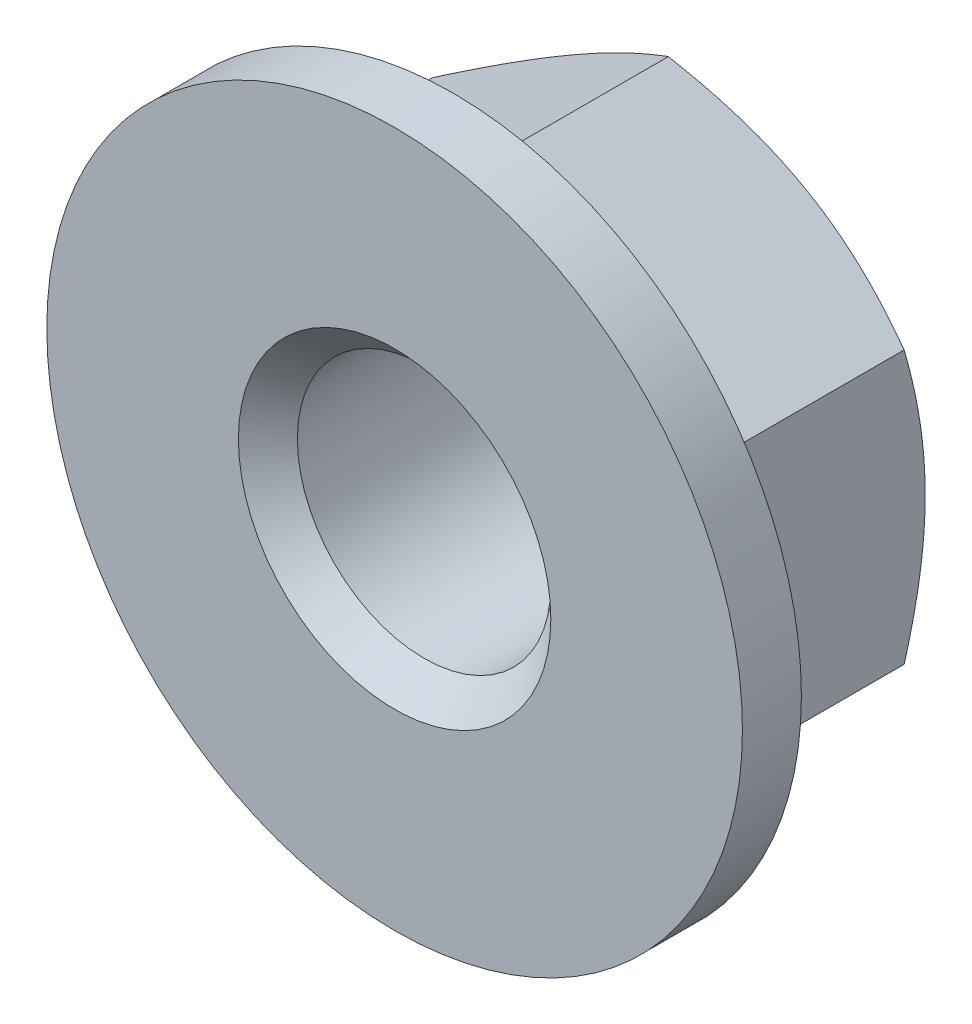
SolidWorks part; units mm, degrees
note: '?' marks a value the reader was unsure of.
ref_plane "前视基准面" through (0, 0, 0) normal (0, 0, 1) x (1, 0, 0)
ref_plane "上视基准面" through (0, 0, 0) normal (0, 1, 0) x (1, 0, 0)
ref_plane "右视基准面" through (0, 0, 0) normal (1, 0, 0) x (0, 0, -1)
sketch "草图1" plane through (0, 0, 0) normal (0, 0, 1) x (1, 0, 0)
  line L1 (0, 4.6188) -> (-4, 2.3094)
  line L2 (-4, 2.3094) -> (-4, -2.3094)
  line L3 (-4, -2.3094) -> (0, -4.6188)
  line L4 (0, -4.6188) -> (4, -2.3094)
  line L5 (4, -2.3094) -> (4, 2.3094)
  line L6 (4, 2.3094) -> (0, 4.6188)
  circle A0 centre (0, 0) radius 4 construction
  dimension "D2" = 8
extrude "凸台-拉伸1" add sketch "草图1" against normal blind 4
sketch "草图2" plane through (0, 0, 0) normal (1, 0, 0) x (0, 0, -1)
  line L0 (0, 4.6188) -> (0.3573, 4.6188)
  line L1 (0, 4.6188) -> (0, 4)
  line L2 (4, 4.6188) -> (0, 4.6188) construction
  line L3 (0.3573, 4.6188) -> (0, 4)
  line L5 (0, 0) -> (4, 0) construction
  line L6 (4, -2.3094) -> (4, 2.3094) construction
  line L7 (4, 4) -> (3.6427, 4.6188)
  line L8 (4, 2.3094) -> (4, 4.6188) construction
  line L9 (3.6427, 4.6188) -> (4, 4.6188)
  line L10 (4, 4.6188) -> (4, 4)
  dimension "D1" = 8
  dimension "D2" = 30
revolve "切除-旋转1" cut sketch "草图2" angle 360 about L5
sketch "草图3" plane through (0, 0, 0) normal (0, 0, 1) x (1, 0, 0)
  circle A0 centre (0, 0) radius 5.9
  dimension "D1" = 11.8
extrude "凸台-拉伸2" add sketch "草图3" along normal blind 1
sketch "草图4" plane through (0, 0, -4) normal (0, 0, -1) x (-1, 0, 0)
  circle A0 centre (0, 0) radius 2.15
  dimension "D1" = 4.3
extrude "切除-拉伸1" cut sketch "草图4" against normal through all
cosmetic thread "装饰螺纹线1"
chamfer "倒角1" distance 0.5 angle 45 2 edges at (-2.15, 0, -4) (-2.15, 0, 1)
sketch "草图5" plane through (0, 0, 0) normal (0, 0, 1) x (1, 0, 0)
  line L1 (0, 4.6188) -> (-4, 2.3094)
  line L2 (-4, 2.3094) -> (-4, -2.3094)
  line L3 (-4, -2.3094) -> (0, -4.6188)
  line L4 (0, -4.6188) -> (4, -2.3094)
  line L5 (4, -2.3094) -> (4, 2.3094)
  line L6 (4, 2.3094) -> (0, 4.6188)
  circle A0 centre (0, 0) radius 4 construction
  circle A1 centre (0, 0) radius 2.15
  dimension "D1" = 8
  dimension "D2" = 4.3
extrude "凸台-拉伸3" [suppressed] add sketch "草图5" against normal blind 2.4
cosmetic thread "装饰螺纹线2" [suppressed] parameters "D2"=3
sketch "草图6" [suppressed] plane through (0, 0, 0) normal (1, 0, 0) x (0, 0, -1)
  line L0 (0.2456, 3.1754) -> (0, 2.75)
  line L1 (2.4, 3.1754) -> (0, 3.1754) construction
  line L3 (0, 2.75) -> (0, 3.1754)
  line L4 (0, 3.1754) -> (0.2456, 3.1754)
  line L5 (0, 0) -> (2.4, 0) construction
  line L6 (2.4, -1.5877) -> (2.4, 1.5877) construction
  line L7 (0, 1.5877) -> (0, 3.1754) construction
  line L8 (2.1544, 3.1754) -> (2.4, 2.75)
  line L10 (2.4, 1.5877) -> (2.4, 3.1754) construction
  line L11 (2.4, 3.1754) -> (2.1544, 3.1754)
  line L12 (2.4, 2.75) -> (2.4, 3.1754)
  dimension "D1" = 8
  dimension "D2" = 30
revolve "切除-旋转2" [suppressed] cut sketch "草图6" angle 360 about L5
chamfer "倒角2" [suppressed] distance 0.5 angle 45
sketch "草图7" [suppressed] plane through (0, 0, 0) normal (1, 0, 0) x (0, 0, -1)
  line L0 (0, 0) -> (-3.6, 0)
  line L1 (2.4, 0) -> (2.4, 2.3816) construction
  line L2 (0, 0) -> (0, 2.3)
  line L3 (-1.3, 2.3) -> (0, 2.3)
  line L4 (0, 2.3816) -> (0, 0) construction
  line L5 (-5.267, 0) -> (3.7229, 0) construction
  arc A1 (-1.3, 2.3) -> (-3.6, 0) centre (-1.3, 0) ccw
  dimension "D2" = 11.8
  dimension "D3" = 2.3
  dimension "D1" = 5
revolve "旋转1" [suppressed] add sketch "草图7" angle 360 about L0
shell "抽壳1" [suppressed] thickness 1
combine bodies "组合1" [suppressed] operation type? add bodies to combine 111 112
fillet "圆角3" [suppressed] radius 0.45
